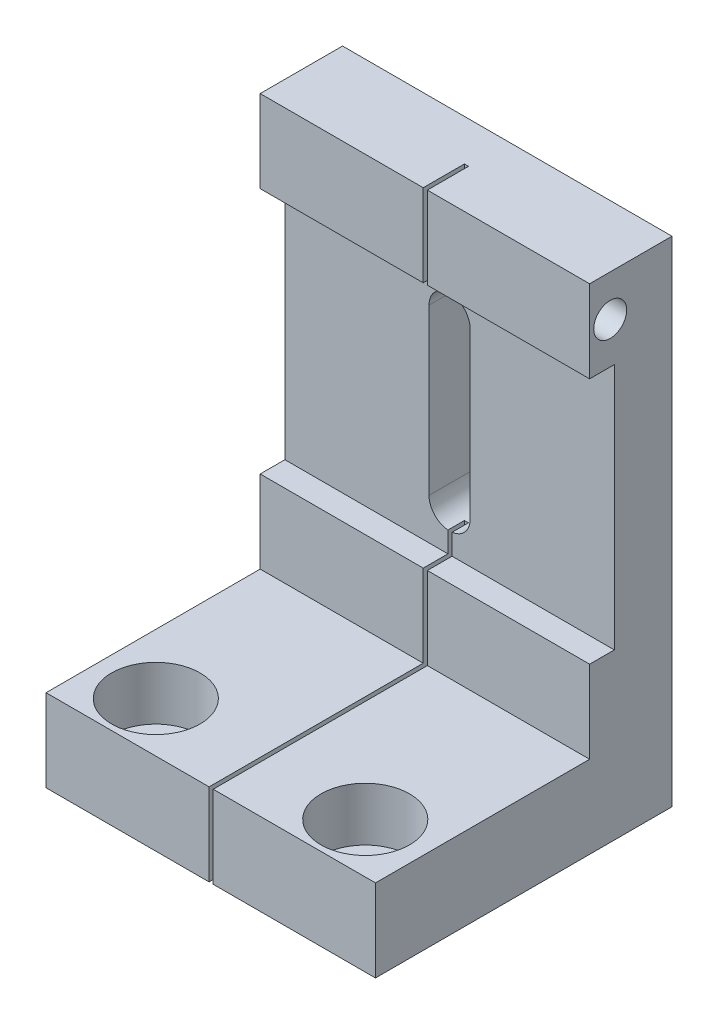
SolidWorks part; units mm, degrees
ref_plane "Front Plane" through (0, 0, 0) normal (0, 0, 1) x (1, 0, 0)
ref_plane "Top Plane" through (0, 0, 0) normal (0, 1, 0) x (1, 0, 0)
ref_plane "Right Plane" through (0, 0, 0) normal (1, 0, 0) x (0, 0, -1)
sketch "Sketch1" plane through (0, 0, 0) normal (0, 0, 1) x (1, 0, 0)
  line L1 (0, 0) -> (-40, 0)
  line L2 (0, 0) -> (0, -60)
  line L3 (0, -60) -> (-40, -60)
  line L4 (-40, 0) -> (-40, -60)
  dimension "D1" = 40
  dimension "D2" = 60
extrude "Boss-Extrude1" add sketch "Sketch1" along normal blind 10
sketch "Sketch2" plane through (0, 0, 10) normal (0, 0, 1) x (1, 0, 0)
  line L0 (-20, -15) -> (-20, -35) construction
  line L1 (-17.5, -15) -> (-17.5, -35)
  line L2 (-22.5, -15) -> (-22.5, -35)
  line L4 (-40, -60) -> (0, -60) construction
  line L5 (0, 0) -> (-40, 0) construction
  line L6 (-20, 0) -> (-20, -5.6142) construction
  arc A0 (-17.5, -15) -> (-22.5, -15) centre (-20, -15) ccw
  arc A1 (-22.5, -35) -> (-17.5, -35) centre (-20, -35) ccw
  point P2 (-20, -25)
  dimension "D1" = 5
  dimension "D2" = 20
  dimension "D4" = 35
extrude "Cut-Extrude1" cut sketch "Sketch2" against normal through all
sketch "Sketch5" plane through (0, 0, 0) normal (1, 0, 0) x (0, 0, -1)
  line L0 (-7, -10) -> (-10, -10)
  line L1 (-10, -60) -> (-10, 0) construction
  line L2 (-7, -10) -> (-7, -40)
  line L3 (-10, -60) -> (0, -60) construction
  line L4 (-7, -40) -> (-10, -40)
  line L7 (-10, -10) -> (-10, -40)
  dimension "D1" = 3
  dimension "D4" = 30
  dimension "D5" = 20
extrude "Cut-Extrude4" cut sketch "Sketch5" against normal through all
sketch "Sketch6" plane through (0, 0, 10) normal (0, 0, 1) x (1, 0, 0)
  line L0 (-40, -40) -> (-40, -60) construction
  line L1 (0, -60) -> (-40, -60)
  line L2 (0, -60) -> (0, -50)
  line L3 (0, -50) -> (-40, -50)
  line L4 (-40, -60) -> (-40, -50)
  dimension "D1" = 10
extrude "Boss-Extrude2" add sketch "Sketch6" along normal blind 26
sketch "Sketch7" plane through (0, -50, 0) normal (0, 1, 0) x (1, 0, 0)
  line L3 (-40, -36) -> (-40, -10) construction
  circle A0 centre (-4.0875, -15.1829) radius 2
  circle A1 centre (-35.875, -15.1829) radius 2
  dimension "D1" = 4
  dimension "D2" = 4
  dimension "D3" = 4.125
  dimension "D5" = 31.7875
extrude "Cut-Extrude5" [suppressed] cut sketch "Sketch7" against normal blind 40
sketch "Sketch8" plane through (0, 0, 0) normal (0, 1, 0) x (1, 0, 0)
  line L2 (-20.2, -36) -> (-19.7, -36)
  line L5 (-20.2, -36) -> (-20.2, -5)
  line L7 (0, -36) -> (-40, -36) construction
  line L9 (-20.2, -5) -> (-19.7, -5)
  line L10 (-19.7, -36) -> (-19.7, -5)
  line L11 (-22.5, 0) -> (-22.5, -7) construction
  dimension "D1" = 0.5
  dimension "D2" = 2.3
  dimension "D3" = 31
extrude "Cut-Extrude7" cut sketch "Sketch8" against normal up to surface (60 mm away) up to face at (-20, -60, 18)
sketch "Sketch9" plane through (0, -60, 0) normal (0, -1, 0) x (1, 0, 0)
  line L3 (0, 36) -> (0, 0) construction
  line L5 (-40, 7) -> (-20.2, 7) construction
  circle A0 centre (-32.73, 5) radius 2
  circle A1 centre (-7.3, 5) radius 2
  dimension "D1" = 4
  dimension "D3" = 7.3
  dimension "D4" = 4
  dimension "D2" = 25.43
extrude "Cut-Extrude9" [suppressed] cut sketch "Sketch9" against normal blind 15
sketch "Sketch10" plane through (0, 0, 0) normal (1, 0, 0) x (0, 0, -1)
  line L1 (-10, 0) -> (0, 0) construction
  line L2 (-10, -10) -> (-10, 0) construction
  circle A0 centre (-7.5, -5) radius 2
  dimension "D1" = 4
  dimension "D2" = 5
  dimension "D3" = 2.5
extrude "Cut-Extrude10" cut sketch "Sketch10" against normal blind 30
sketch "Sketch12" plane through (0, -60, 0) normal (0, -1, 0) x (1, 0, 0)
  line L0 (-32.73, 29.94) -> (-32.73, 4.51) construction
  line L1 (-32.73, 4.51) -> (-7.3, 4.51) construction
  line L2 (-7.3, 4.51) -> (-7.3, 29.94) construction
  line L3 (-7.3, 29.94) -> (-32.73, 29.94) construction
  line L4 (-40, 7) -> (-20.2, 7) construction
  line L6 (0, 36) -> (0, 0) construction
  line L10 (-19.7, 36) -> (0, 36) construction
  line L11 (-40, 0) -> (-40, 36) construction
  circle A0 centre (-7.3, 29.94) radius 3.4
  circle A1 centre (-32.73, 29.94) radius 3.4
  circle A2 centre (-32.73, 4.51) radius 2.49
  circle A3 centre (-7.3, 4.51) radius 2.49
  circle A4 centre (-7.3, 29.94) radius 5.375 construction
  circle A5 centre (-32.73, 4.54) radius 3.4 [skipped]
  circle A6 centre (-7.3, 4.54) radius 3.4 [skipped]
  dimension "D1" = 6.8
  dimension "D2" = 2
  dimension "D3" = 2
  dimension "D4" = 10.75
  dimension "D6" = 7.3
  dimension "D7" = 25.43
  dimension "D8" = 4.98
  dimension "D9" = 25.43
  dimension "D11" = 6.06
  dimension "D5" = 2
  dimension "D12" = 7.27
extrude "Cut-Extrude13" cut sketch "Sketch12" against normal up to surface (10 mm away) up to face at (-9.85, -50, 23)
sketch "Sketch14" plane through (0, -50, 0) normal (0, 1, 0) x (1, 0, 0)
  line L0 (-32.73, -29.94) -> (18.13, -29.94) construction
  circle A0 centre (-32.73, -29.94) radius 5.375
  circle A1 centre (-7.3, -29.94) radius 5.375
  dimension "D1" = 10.75
  dimension "D3" = 25.43
  dimension "D2" = 2
extrude "Cut-Extrude14" cut sketch "Sketch14" against normal blind 6.5
equation "\"inch\"= 25.43"
equation "\"D5@Sketch7\"=\"inch\"*1.25"
equation "\"D2@Sketch9\"=\"inch\""
equation "\"D7@Sketch12\"=\"inch\""
equation "\"D9@Sketch12\"=\"inch\""
equation "\"D3@Sketch14\"=\"inch\""
